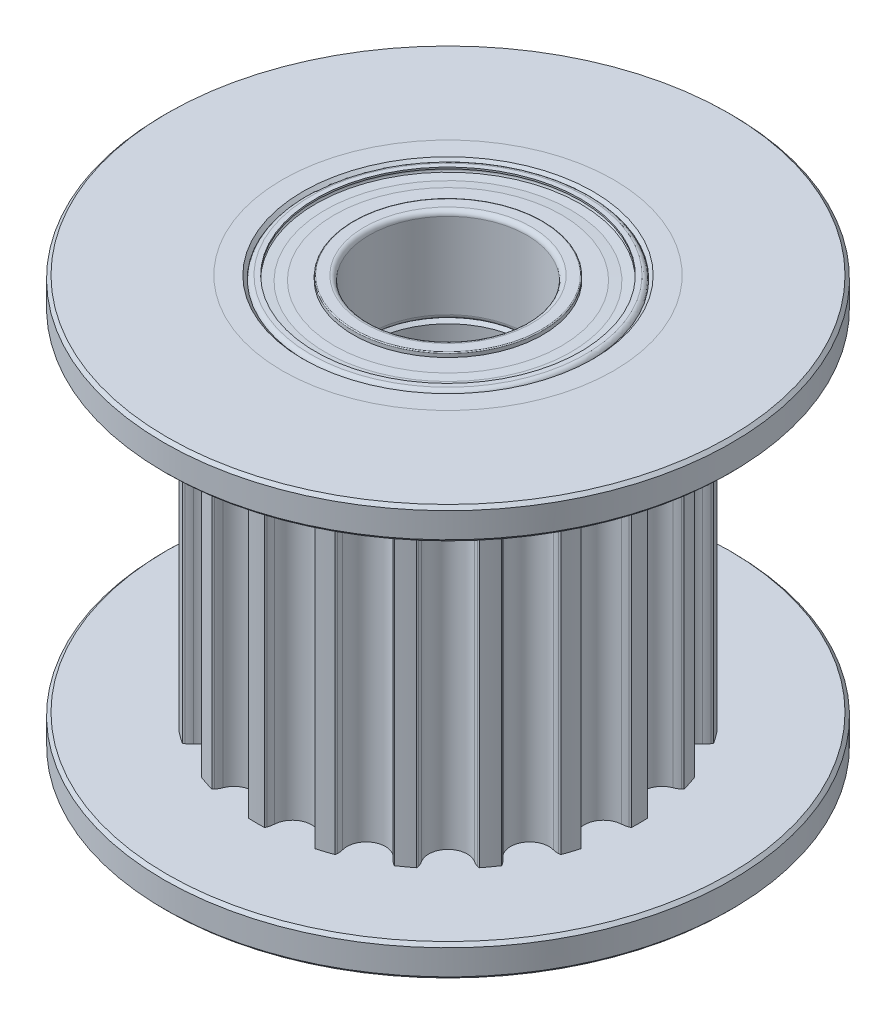
SolidWorks part; units mm, degrees
material "6061-T6 (SS)"
ref_plane "Přední rovina" through (0, 0, 0) normal (0, 0, 1) x (1, 0, 0)
ref_plane "Horní rovina" through (0, 0, 0) normal (0, 1, 0) x (1, 0, 0)
ref_plane "Pravá rovina" through (0, 0, 0) normal (1, 0, 0) x (0, 0, -1)
sketch "Skica1" plane through (0, 0, 0) normal (0, 0, 1) x (1, 0, 0)
  line L0 (4.5, 13) -> (5.25, 13)
  line L1 (5.25, 13) -> (5.25, 12)
  line L2 (5.25, 12) -> (6.075, 12)
  line L3 (6.075, 12) -> (6.075, 1)
  line L4 (6.075, 1) -> (5.25, 1)
  line L5 (5.25, 1) -> (5.25, 0)
  line L6 (5.25, 0) -> (4.5, 0)
  line L8 (4.5, 13) -> (4.5, 10)
  line L9 (4.5, 10) -> (2.5, 10)
  line L10 (2.5, 10) -> (2.5, 3)
  line L11 (2.5, 3) -> (4.5, 3)
  line L12 (4.5, 3) -> (4.5, 0)
  line L13 (0, 0) -> (0, -4.1646) construction
  dimension "D1" = 13
  dimension "D2" = 11
  dimension "D3" = 4.5
  dimension "D4" = 2.5
  dimension "D5" = 6.075
  dimension "D6" = 3
  dimension "D7" = 5.25
revolve "Rotovat1" add sketch "Skica1" angle 360 about L13
chamfer "Zkosení1" distance 0.1 angle 45 4 edges at (0, 3, 2.5) (0, 0, 4.5) (0, 10, 2.5) (0, 13, 4.5)
fillet "Zaoblit1" radius 0.1 2 edges at (0, 3, 4.5) (0, 10, 4.5)
sketch "Skica11" plane through (0, 12, 0) normal (0, 1, 0) x (1, 0, 0)
  line L0 (0, -55) -> (0, 55) construction
  line L1 (-55, 0) -> (55, 0) construction
  point P5 (0, 6.1087)
  arc B0 (-3.6824, -4.5256) -> (-4.5256, -3.6824) centre (-4.1938, -4.1938) ccw
  arc B1 (-3.6824, -4.5256) -> (-3.7624, -4.7003) centre (-3.1284, -4.885) ccw
  arc B2 (-3.7624, -4.7003) -> (-3.7672, -4.8088) centre (-3.5429, -4.7643) ccw
  arc B3 (-3.7672, -4.8088) -> (-3.4093, -5.0688) centre (0, 0) ccw
  arc B4 (-3.4093, -5.0688) -> (-3.3076, -5.0308) centre (-3.4362, -4.8418) ccw
  arc B5 (-3.3076, -5.0308) -> (-3.1662, -4.9006) centre (-3.6792, -4.4848) ccw
  arc B6 (-2.1037, -5.442) -> (-3.1662, -4.9006) centre (-2.6926, -5.2845) ccw
  arc B7 (-2.1037, -5.442) -> (-2.1258, -5.6329) centre (-1.4657, -5.6126) ccw
  arc B8 (-2.1258, -5.6329) -> (-2.0968, -5.7376) centre (-1.8973, -5.6259) ccw
  arc B9 (-2.0968, -5.7376) -> (-1.6761, -5.8742) centre (0, 0) ccw
  arc B10 (-1.6761, -5.8742) -> (-1.5911, -5.8066) centre (-1.7719, -5.6667) ccw
  arc B11 (-1.5911, -5.8066) -> (-1.4968, -5.6392) centre (-2.1132, -5.4022) ccw
  arc B12 (-0.319, -5.8257) -> (-1.4968, -5.6392) centre (-0.9278, -5.8579) ccw
  arc B13 (-0.319, -5.8257) -> (-0.2811, -6.0141) centre (0.3404, -5.7909) ccw
  arc B14 (-0.2811, -6.0141) -> (-0.2211, -6.1047) centre (-0.0659, -5.9369) ccw
  arc B15 (-0.2211, -6.1047) -> (0.2211, -6.1047) centre (0, 0) ccw
  arc B16 (0.2211, -6.1047) -> (0.2811, -6.0141) centre (0.0659, -5.9369) ccw
  arc B17 (0.2811, -6.0141) -> (0.319, -5.8257) centre (-0.3404, -5.7909) ccw
  arc B18 (1.4968, -5.6392) -> (0.319, -5.8257) centre (0.9278, -5.8579) ccw
  arc B19 (1.4968, -5.6392) -> (1.5911, -5.8066) centre (2.1132, -5.4022) ccw
  arc B20 (1.5911, -5.8066) -> (1.6761, -5.8742) centre (1.7719, -5.6667) ccw
  arc B21 (1.6761, -5.8742) -> (2.0968, -5.7376) centre (0, 0) ccw
  arc B22 (2.0968, -5.7376) -> (2.1258, -5.6329) centre (1.8973, -5.6259) ccw
  arc B23 (2.1258, -5.6329) -> (2.1037, -5.442) centre (1.4657, -5.6126) ccw
  arc B24 (3.1662, -4.9006) -> (2.1037, -5.442) centre (2.6926, -5.2845) ccw
  arc B25 (3.1662, -4.9006) -> (3.3076, -5.0308) centre (3.6792, -4.4848) ccw
  arc B26 (3.3076, -5.0308) -> (3.4093, -5.0688) centre (3.4362, -4.8418) ccw
  arc B27 (3.4093, -5.0688) -> (3.7672, -4.8088) centre (0, 0) ccw
  arc B28 (3.7672, -4.8088) -> (3.7624, -4.7003) centre (3.5429, -4.7643) ccw
  arc B29 (3.7624, -4.7003) -> (3.6824, -4.5256) centre (3.1284, -4.885) ccw
  arc B30 (4.5256, -3.6824) -> (3.6824, -4.5256) centre (4.1938, -4.1938) ccw
  arc B31 (4.5256, -3.6824) -> (4.7003, -3.7624) centre (4.885, -3.1284) ccw
  arc B32 (4.7003, -3.7624) -> (4.8088, -3.7672) centre (4.7643, -3.5429) ccw
  arc B33 (4.8088, -3.7672) -> (5.0688, -3.4093) centre (0, 0) ccw
  arc B34 (5.0688, -3.4093) -> (5.0308, -3.3076) centre (4.8418, -3.4362) ccw
  arc B35 (5.0308, -3.3076) -> (4.9006, -3.1662) centre (4.4848, -3.6792) ccw
  arc B36 (5.442, -2.1037) -> (4.9006, -3.1662) centre (5.2845, -2.6926) ccw
  arc B37 (5.442, -2.1037) -> (5.6329, -2.1258) centre (5.6126, -1.4657) ccw
  arc B38 (5.6329, -2.1258) -> (5.7376, -2.0968) centre (5.6259, -1.8973) ccw
  arc B39 (5.7376, -2.0968) -> (5.8742, -1.6761) centre (0, 0) ccw
  arc B40 (5.8742, -1.6761) -> (5.8066, -1.5911) centre (5.6667, -1.7719) ccw
  arc B41 (5.8066, -1.5911) -> (5.6392, -1.4968) centre (5.4022, -2.1132) ccw
  arc B42 (5.8257, -0.319) -> (5.6392, -1.4968) centre (5.8579, -0.9278) ccw
  arc B43 (5.8257, -0.319) -> (6.0141, -0.2811) centre (5.7909, 0.3404) ccw
  arc B44 (6.0141, -0.2811) -> (6.1047, -0.2211) centre (5.9369, -0.0659) ccw
  arc B45 (6.1047, -0.2211) -> (6.1047, 0.2211) centre (0, 0) ccw
  arc B46 (6.1047, 0.2211) -> (6.0141, 0.2811) centre (5.9369, 0.0659) ccw
  arc B47 (6.0141, 0.2811) -> (5.8257, 0.319) centre (5.7909, -0.3404) ccw
  arc B48 (5.6392, 1.4968) -> (5.8257, 0.319) centre (5.8579, 0.9278) ccw
  arc B49 (5.6392, 1.4968) -> (5.8066, 1.5911) centre (5.4022, 2.1132) ccw
  arc B50 (5.8066, 1.5911) -> (5.8742, 1.6761) centre (5.6667, 1.7719) ccw
  arc B51 (5.8742, 1.6761) -> (5.7376, 2.0968) centre (0, 0) ccw
  arc B52 (5.7376, 2.0968) -> (5.6329, 2.1258) centre (5.6259, 1.8973) ccw
  arc B53 (5.6329, 2.1258) -> (5.442, 2.1037) centre (5.6126, 1.4657) ccw
  arc B54 (4.9006, 3.1662) -> (5.442, 2.1037) centre (5.2845, 2.6926) ccw
  arc B55 (4.9006, 3.1662) -> (5.0308, 3.3076) centre (4.4848, 3.6792) ccw
  arc B56 (5.0308, 3.3076) -> (5.0688, 3.4093) centre (4.8418, 3.4362) ccw
  arc B57 (5.0688, 3.4093) -> (4.8088, 3.7672) centre (0, 0) ccw
  arc B58 (4.8088, 3.7672) -> (4.7003, 3.7624) centre (4.7643, 3.5429) ccw
  arc B59 (4.7003, 3.7624) -> (4.5256, 3.6824) centre (4.885, 3.1284) ccw
  arc B60 (3.6824, 4.5256) -> (4.5256, 3.6824) centre (4.1938, 4.1938) ccw
  arc B61 (3.6824, 4.5256) -> (3.7624, 4.7003) centre (3.1284, 4.885) ccw
  arc B62 (3.7624, 4.7003) -> (3.7672, 4.8088) centre (3.5429, 4.7643) ccw
  arc B63 (3.7672, 4.8088) -> (3.4093, 5.0688) centre (0, 0) ccw
  arc B64 (3.4093, 5.0688) -> (3.3076, 5.0308) centre (3.4362, 4.8418) ccw
  arc B65 (3.3076, 5.0308) -> (3.1662, 4.9006) centre (3.6792, 4.4848) ccw
  arc B66 (2.1037, 5.442) -> (3.1662, 4.9006) centre (2.6926, 5.2845) ccw
  arc B67 (2.1037, 5.442) -> (2.1258, 5.6329) centre (1.4657, 5.6126) ccw
  arc B68 (2.1258, 5.6329) -> (2.0968, 5.7376) centre (1.8973, 5.6259) ccw
  arc B69 (2.0968, 5.7376) -> (1.6761, 5.8742) centre (0, 0) ccw
  arc B70 (1.6761, 5.8742) -> (1.5911, 5.8066) centre (1.7719, 5.6667) ccw
  arc B71 (1.5911, 5.8066) -> (1.4968, 5.6392) centre (2.1132, 5.4022) ccw
  arc B72 (0.319, 5.8257) -> (1.4968, 5.6392) centre (0.9278, 5.8579) ccw
  arc B73 (0.319, 5.8257) -> (0.2811, 6.0141) centre (-0.3404, 5.7909) ccw
  arc B74 (0.2811, 6.0141) -> (0.2211, 6.1047) centre (0.0659, 5.9369) ccw
  arc B75 (0.2211, 6.1047) -> (-0.2211, 6.1047) centre (0, 0) ccw
  arc B76 (-0.2211, 6.1047) -> (-0.2811, 6.0141) centre (-0.0659, 5.9369) ccw
  arc B77 (-0.2811, 6.0141) -> (-0.319, 5.8257) centre (0.3404, 5.7909) ccw
  arc B78 (-1.4968, 5.6392) -> (-0.319, 5.8257) centre (-0.9278, 5.8579) ccw
  arc B79 (-1.4968, 5.6392) -> (-1.5911, 5.8066) centre (-2.1132, 5.4022) ccw
  arc B80 (-1.5911, 5.8066) -> (-1.6761, 5.8742) centre (-1.7719, 5.6667) ccw
  arc B81 (-1.6761, 5.8742) -> (-2.0968, 5.7376) centre (0, 0) ccw
  arc B82 (-2.0968, 5.7376) -> (-2.1258, 5.6329) centre (-1.8973, 5.6259) ccw
  arc B83 (-2.1258, 5.6329) -> (-2.1037, 5.442) centre (-1.4657, 5.6126) ccw
  arc B84 (-3.1662, 4.9006) -> (-2.1037, 5.442) centre (-2.6926, 5.2845) ccw
  arc B85 (-3.1662, 4.9006) -> (-3.3076, 5.0308) centre (-3.6792, 4.4848) ccw
  arc B86 (-3.3076, 5.0308) -> (-3.4093, 5.0688) centre (-3.4362, 4.8418) ccw
  arc B87 (-3.4093, 5.0688) -> (-3.7672, 4.8088) centre (0, 0) ccw
  arc B88 (-3.7672, 4.8088) -> (-3.7624, 4.7003) centre (-3.5429, 4.7643) ccw
  arc B89 (-3.7624, 4.7003) -> (-3.6824, 4.5256) centre (-3.1284, 4.885) ccw
  arc B90 (-4.5256, 3.6824) -> (-3.6824, 4.5256) centre (-4.1938, 4.1938) ccw
  arc B91 (-4.5256, 3.6824) -> (-4.7003, 3.7624) centre (-4.885, 3.1284) ccw
  arc B92 (-4.7003, 3.7624) -> (-4.8088, 3.7672) centre (-4.7643, 3.5429) ccw
  arc B93 (-4.8088, 3.7672) -> (-5.0688, 3.4093) centre (0, 0) ccw
  arc B94 (-5.0688, 3.4093) -> (-5.0308, 3.3076) centre (-4.8418, 3.4362) ccw
  arc B95 (-5.0308, 3.3076) -> (-4.9006, 3.1662) centre (-4.4848, 3.6792) ccw
  arc B96 (-5.442, 2.1037) -> (-4.9006, 3.1662) centre (-5.2845, 2.6926) ccw
  arc B97 (-5.442, 2.1037) -> (-5.6329, 2.1258) centre (-5.6126, 1.4657) ccw
  arc B98 (-5.6329, 2.1258) -> (-5.7376, 2.0968) centre (-5.6259, 1.8973) ccw
  arc B99 (-5.7376, 2.0968) -> (-5.8742, 1.6761) centre (0, 0) ccw
  arc B100 (-5.8742, 1.6761) -> (-5.8066, 1.5911) centre (-5.6667, 1.7719) ccw
  arc B101 (-5.8066, 1.5911) -> (-5.6392, 1.4968) centre (-5.4022, 2.1132) ccw
  arc B102 (-5.8257, 0.319) -> (-5.6392, 1.4968) centre (-5.8579, 0.9278) ccw
  arc B103 (-5.8257, 0.319) -> (-6.0141, 0.2811) centre (-5.7909, -0.3404) ccw
  arc B104 (-6.0141, 0.2811) -> (-6.1047, 0.2211) centre (-5.9369, 0.0659) ccw
  arc B105 (-6.1047, 0.2211) -> (-6.1047, -0.2211) centre (0, 0) ccw
  arc B106 (-6.1047, -0.2211) -> (-6.0141, -0.2811) centre (-5.9369, -0.0659) ccw
  arc B107 (-6.0141, -0.2811) -> (-5.8257, -0.319) centre (-5.7909, 0.3404) ccw
  arc B108 (-5.6392, -1.4968) -> (-5.8257, -0.319) centre (-5.8579, -0.9278) ccw
  arc B109 (-5.6392, -1.4968) -> (-5.8066, -1.5911) centre (-5.4022, -2.1132) ccw
  arc B110 (-5.8066, -1.5911) -> (-5.8742, -1.6761) centre (-5.6667, -1.7719) ccw
  arc B111 (-5.8742, -1.6761) -> (-5.7376, -2.0968) centre (0, 0) ccw
  arc B112 (-5.7376, -2.0968) -> (-5.6329, -2.1258) centre (-5.6259, -1.8973) ccw
  arc B113 (-5.6329, -2.1258) -> (-5.442, -2.1037) centre (-5.6126, -1.4657) ccw
  arc B114 (-4.9006, -3.1662) -> (-5.442, -2.1037) centre (-5.2845, -2.6926) ccw
  arc B115 (-4.9006, -3.1662) -> (-5.0308, -3.3076) centre (-4.4848, -3.6792) ccw
  arc B116 (-5.0308, -3.3076) -> (-5.0688, -3.4093) centre (-4.8418, -3.4362) ccw
  arc B117 (-5.0688, -3.4093) -> (-4.8088, -3.7672) centre (0, 0) ccw
  arc B118 (-4.8088, -3.7672) -> (-4.7003, -3.7624) centre (-4.7643, -3.5429) ccw
  arc B119 (-4.7003, -3.7624) -> (-4.5256, -3.6824) centre (-4.885, -3.1284) ccw
sketch_block_instance "Blok1-1"
sketch_block "Blok1"
extrude "Odebrat vysunutím1" cut sketch "Skica11" against normal through all flip side to cut
sketch "Skica10" plane through (0, 13, 0) normal (0, 1, 0) x (1, 0, 0)
  circle A0 centre (0, 0) radius 9
  circle A1 centre (0, 0) radius 5.25 construction
  circle A2 centre (0, 0) radius 5.25
  dimension "D1" = 18
extrude "Přidat vysunutím1" add sketch "Skica10" against normal up to surface (1 mm away) separate body up to face at (0, 12, 5.25)
sketch "Skica12" plane through (0, 0, 0) normal (0, -1, 0) x (1, 0, 0)
  circle A0 centre (0, 0) radius 9
  circle A1 centre (0, 0) radius 5.25 construction
  circle A2 centre (0, 0) radius 5.25
  circle A3 centre (0, 0) radius 9 construction
extrude "Přidat vysunutím2" add sketch "Skica12" against normal up to surface (1 mm away) separate body up to face at (0, 1, 5.25)
chamfer "Zkosení2" distance 0.1 angle 45 2 edges at (0, 12, -9) (0, 13, 9)
chamfer "Zkosení3" distance 0.1 angle 45 2 edges at (0, 0, -9) (0, 1, 9)
sketch "Skica4" plane through (0, 0, 0) normal (0, 0, 1) x (1, 0, 0)
  line L0 (4.5, 12.85) -> (4.5, 10.15)
  line L1 (4.35, 10) -> (4.2, 10)
  line L2 (4.2, 10) -> (4.2, 10.05)
  line L3 (3.85, 10.2828) -> (4.2132, 10.229)
  line L4 (3.85, 10.2828) -> (3.85, 11.0528)
  line L5 (3.85, 11.9472) -> (3.85, 12.7172)
  line L6 (3.85, 12.7172) -> (4.2132, 12.771)
  line L7 (4.35, 13) -> (4.2, 13)
  line L8 (4.2, 13) -> (4.2, 12.95)
  line L9 (0, 0) -> (0, 18.4294) construction
  line L10 (4.4, 10) -> (-4.4, 10) construction
  arc A0 (4.35, 13) -> (4.5, 12.85) centre (4.35, 12.85) cw
  arc A1 (4.35, 10) -> (4.5, 10.15) centre (4.35, 10.15) ccw
  arc A2 (4.2, 12.95) -> (4.2132, 12.771) centre (4.2, 12.86) cw
  arc A3 (3.85, 11.9472) -> (3.85, 11.0528) centre (3.45, 11.5) cw
  arc A4 (4.2, 10.05) -> (4.2132, 10.229) centre (4.2, 10.14) ccw
  point P26 (4.5, 11.5)
  point P29 (4.275, 10)
  dimension "D3" = 0.09
  dimension "D6" = 0.15
  dimension "D7" = 0.6
  dimension "D1" = 4.5
  dimension "D2" = 3.85
  dimension "D4" = 0.05
  dimension "D5" = 0.15
  dimension "D8" = 0.77
  dimension "D9" = 3
  dimension "D10" = 1.05
revolve "Rotovat2" add sketch "Skica4" angle 360 about L9
sketch "Skica5" plane through (0, 0, 0) normal (0, 0, 1) x (1, 0, 0)
  line L0 (2.5, 12.85) -> (2.5, 10.15)
  line L1 (2.65, 13) -> (2.97, 13)
  line L2 (3, 12.97) -> (3, 12.86)
  line L3 (3, 12.86) -> (3.6, 12.86)
  line L4 (3.6, 12.86) -> (3.9, 12.84)
  line L5 (3.9, 12.84) -> (4.2, 12.86)
  line L6 (4.2, 12.86) -> (4.2, 12.81)
  line L7 (4.2, 12.81) -> (3.9, 12.77)
  line L8 (3.9, 12.77) -> (3.6, 12.77)
  line L9 (3.6, 12.77) -> (3, 12.81)
  line L10 (3, 12.81) -> (3, 11.8969)
  line L11 (2.65, 10) -> (2.97, 10)
  line L12 (0, 0) -> (0, 20.363) construction
  line L13 (3, 10.03) -> (3, 10.14)
  line L21 (3, 10.19) -> (3, 11.1031)
  line L22 (3, 10.14) -> (3.6, 10.14)
  line L23 (3.6, 10.14) -> (3.8962, 10.1917)
  line L24 (3.8962, 10.1917) -> (4.1924, 10.14)
  line L25 (4.1924, 10.14) -> (4.1924, 10.19)
  line L26 (4.1924, 10.19) -> (3.8975, 10.2581)
  line L27 (3.8975, 10.2581) -> (3.5975, 10.2581)
  line L28 (3.5975, 10.2581) -> (3, 10.19)
  line L29 (-4.2, 10) -> (4.2, 10) construction
  arc A0 (2.65, 10) -> (2.5, 10.15) centre (2.65, 10.15) cw
  arc A1 (2.65, 13) -> (2.5, 12.85) centre (2.65, 12.85) ccw
  arc A2 (3, 12.97) -> (2.97, 13) centre (2.97, 12.97) ccw
  arc A3 (3, 10.03) -> (2.97, 10) centre (2.97, 10.03) cw
  arc A4 (3, 11.8969) -> (3, 11.1031) centre (3.45, 11.5) ccw
  dimension "D3" = 0.15
  dimension "D4" = 0.11
  dimension "D5" = 0.03
  dimension "D7" = 0.6
  dimension "D1" = 2.5
  dimension "D2" = 3
  dimension "D6" = 0.6
  dimension "D8" = 0.95
  dimension "D9" = 3
  dimension "D10" = 1.2
  dimension "D11" = 0.3
  dimension "D12" = 0.05
  dimension "D13" = 0.9
  dimension "D14" = 0.6
  dimension "D15" = 0.09
  dimension "D16" = 0.05
  dimension "D17" = 0.05
revolve "Rotovat3" add sketch "Skica5" angle 360 about L12
sketch "Skica6" plane through (0, 0, 0) normal (0, 0, 1) x (1, 0, 0)
  line L0 (3.45, 12.1) -> (3.45, 10.9)
  line L4 (-4.2, 10) -> (4.2, 10) construction
  arc A0 (3.45, 12.1) -> (3.45, 10.9) centre (3.45, 11.5) cw
  dimension "D1" = 0.6
  dimension "D2" = 1.5
  dimension "D3" = 3.45
revolve "Rotovat4" add sketch "Skica6" angle 360 about L0
pattern_circular "Kruhové pole1" count 8 over 360 about axis through (0, 0, 0) along (0, 1, 0) of bodies 105
sketch "Skica7" plane through (0, 0, 0) normal (0, 0, 1) x (1, 0, 0)
  line L0 (4.5, 2.85) -> (4.5, 0.15)
  line L1 (4.35, 0) -> (4.2, 0)
  line L2 (4.2, 0) -> (4.2, 0.05)
  line L3 (3.85, 0.2828) -> (4.2132, 0.229)
  line L4 (3.85, 0.2828) -> (3.85, 1.0528)
  line L5 (3.85, 1.9472) -> (3.85, 2.7172)
  line L6 (3.85, 2.7172) -> (4.2132, 2.771)
  line L7 (4.35, 3) -> (4.2, 3)
  line L8 (4.2, 3) -> (4.2, 2.95)
  line L9 (0, 0) -> (0, 11.2374) construction
  arc A0 (4.35, 3) -> (4.5, 2.85) centre (4.35, 2.85) cw
  arc A1 (4.35, 0) -> (4.5, 0.15) centre (4.35, 0.15) ccw
  arc A2 (4.2, 2.95) -> (4.2132, 2.771) centre (4.2, 2.86) cw
  arc A3 (3.85, 1.9472) -> (3.85, 1.0528) centre (3.45, 1.5) cw
  arc A4 (4.2, 0.05) -> (4.2132, 0.229) centre (4.2, 0.14) ccw
  point P19 (4.5, 1.5)
  point P20 (4.275, 0)
  dimension "D1" = 0.09
  dimension "D4" = 0.15
  dimension "D5" = 0.6
  dimension "D2" = 0.05
  dimension "D3" = 0.15
  dimension "D6" = 0.77
  dimension "D7" = 3
  dimension "D8" = 1.05
  dimension "D9" = 4.5
  dimension "D10" = 3.85
revolve "Rotovat5" add sketch "Skica7" angle 360 about L9
sketch "Skica8" plane through (0, 0, 0) normal (0, 0, 1) x (1, 0, 0)
  line L0 (2.5, 2.85) -> (2.5, 0.15)
  line L1 (2.65, 3) -> (2.97, 3)
  line L2 (3, 2.97) -> (3, 2.86)
  line L3 (3, 2.86) -> (3.6, 2.86)
  line L4 (3.6, 2.86) -> (3.9, 2.84)
  line L5 (3.9, 2.84) -> (4.2, 2.86)
  line L6 (4.2, 2.86) -> (4.2, 2.81)
  line L7 (4.2, 2.81) -> (3.9, 2.77)
  line L8 (3.9, 2.77) -> (3.6, 2.77)
  line L9 (3.6, 2.77) -> (3, 2.81)
  line L10 (3, 2.81) -> (3, 1.8969)
  line L11 (2.65, 0) -> (2.97, 0)
  line L12 (3, 0.03) -> (3, 0.14)
  line L13 (3, 0.19) -> (3, 1.1031)
  line L14 (3, 0.14) -> (3.6, 0.14)
  line L15 (3.6, 0.14) -> (3.8962, 0.1917)
  line L16 (3.8962, 0.1917) -> (4.1924, 0.14)
  line L17 (4.1924, 0.14) -> (4.1924, 0.19)
  line L18 (4.1924, 0.19) -> (3.8975, 0.2581)
  line L19 (3.8975, 0.2581) -> (3.5975, 0.2581)
  line L20 (3.5975, 0.2581) -> (3, 0.19)
  line L21 (0, 0) -> (0, -2.9362) construction
  arc A0 (2.65, 0) -> (2.5, 0.15) centre (2.65, 0.15) cw
  arc A1 (2.65, 3) -> (2.5, 2.85) centre (2.65, 2.85) ccw
  arc A2 (3, 2.97) -> (2.97, 3) centre (2.97, 2.97) ccw
  arc A3 (3, 0.03) -> (2.97, 0) centre (2.97, 0.03) cw
  arc A4 (3, 1.8969) -> (3, 1.1031) centre (3.45, 1.5) ccw
  dimension "D1" = 0.15
  dimension "D2" = 0.03
  dimension "D5" = 0.6
  dimension "D3" = 0.11
  dimension "D4" = 0.6
  dimension "D6" = 0.95
  dimension "D7" = 3
  dimension "D8" = 1.2
  dimension "D9" = 0.3
  dimension "D10" = 0.05
  dimension "D11" = 0.9
  dimension "D12" = 0.6
  dimension "D13" = 0.09
  dimension "D14" = 0.05
  dimension "D15" = 0.05
  dimension "D16" = 2.5
  dimension "D17" = 3
revolve "Rotovat6" add sketch "Skica8" angle 360 about L21
sketch "Skica9" plane through (0, 0, 0) normal (0, 0, 1) x (1, 0, 0)
  line L0 (3.45, 2.1) -> (3.45, 0.9)
  line L1 (0, -2.351) -> (0, 5.6956) construction
  arc A0 (3.45, 2.1) -> (3.45, 0.9) centre (3.45, 1.5) cw
  dimension "D1" = 0.6
  dimension "D2" = 3.45
  dimension "D3" = 1.5
revolve "Rotovat7" add sketch "Skica9" angle 360 about L0
pattern_circular "Kruhové pole3" count 8 over 360 about axis through (0, 0, 0) along (0, 1, 0) reverse direction yes of bodies 123
